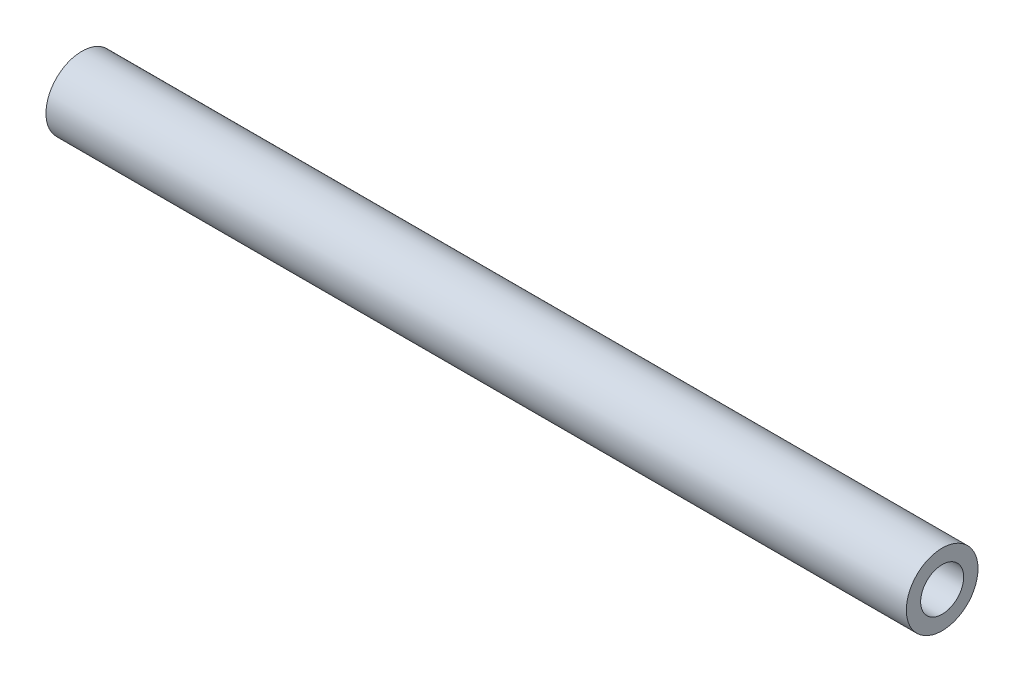
SolidWorks part; units mm, degrees
material "Thornel Mat VMA"
ref_plane "Front Plane" through (0, 0, 0) normal (0, 0, 1) x (1, 0, 0)
ref_plane "Top Plane" through (0, 0, 0) normal (0, 1, 0) x (1, 0, 0)
ref_plane "Right Plane" through (0, 0, 0) normal (1, 0, 0) x (0, 0, -1)
sketch "Sketch1" plane through (0, 0, 0) normal (1, 0, 0) x (0, 0, -1)
  circle A0 centre (0, 0) radius 4.7625
  circle A1 centre (0, 0) radius 7.9375
  dimension "D1" = 9.525
  dimension "D2" = 15.875
extrude "Boss-Extrude1" add sketch "Sketch1" along normal mid plane 190.5
